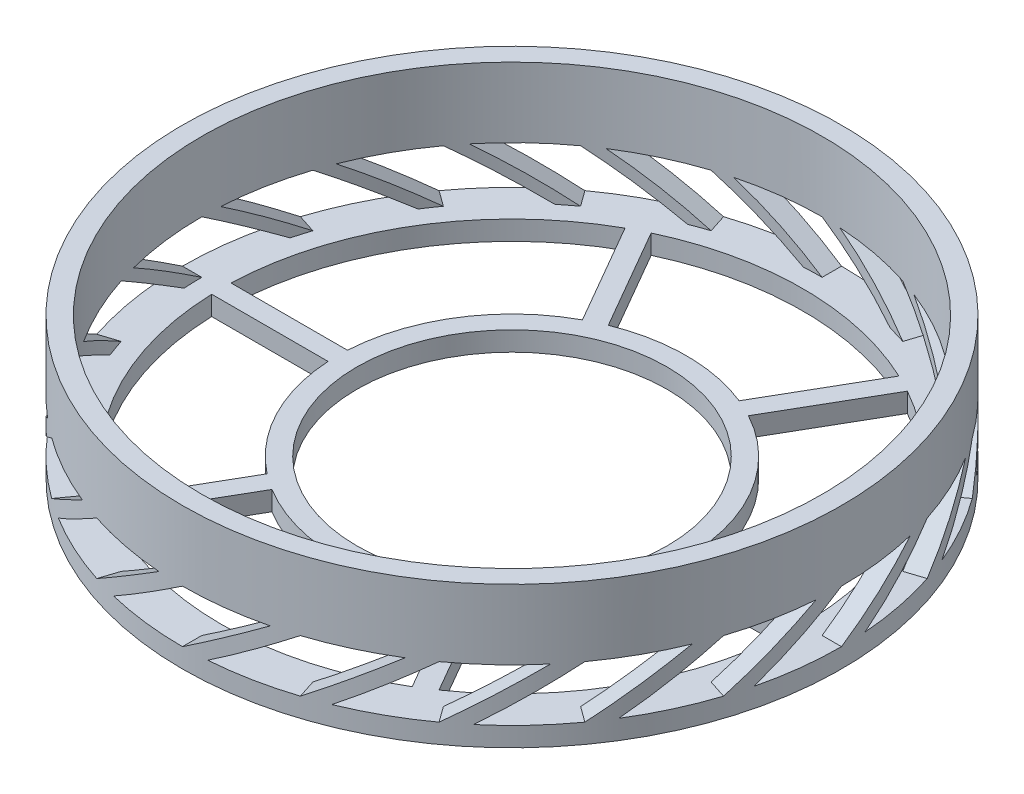
SolidWorks part; units mm, degrees
ref_plane "Front Plane" through (0, 0, 0) normal (0, 0, 1) x (1, 0, 0)
ref_plane "Top Plane" through (0, 0, 0) normal (0, 1, 0) x (1, 0, 0)
ref_plane "Right Plane" through (0, 0, 0) normal (1, 0, 0) x (0, 0, -1)
sketch "Sketch2" plane through (0, 0, 0) normal (0, 1, 0) x (1, 0, 0)
  circle A0 centre (0, 0) radius 26.9875
extrude "Boss-Extrude1" add sketch "Sketch2" along normal blind 11.5951
shell "Shell1" thickness 1.5875 removed face at (0, 11.5951, 26.9875)
ref_axis "Axis1" through (0, 11.5951, 0) along (0, -1, 0)
sketch "Sketch5" plane through (0, 1.5875, 0) normal (0, 1, 0) x (1, 0, 0)
  circle A0 centre (0, 0) radius 12.7
extrude "Cut-Extrude1" cut sketch "Sketch5" against normal through all both and the other way through all
sketch "Sketch6" plane through (0, 0, 0) normal (0, 0, 1) x (1, 0, 0)
  line L0 (0, 1.5875) -> (6.4136, 1.5875)
  line L1 (26.9875, 11.5951) -> (-26.9875, 11.5951) construction
  line L2 (0, 1.5875) -> (-6.4136, 5.8801)
  line L3 (0, 11.5951) -> (0, 8.356)
  line L8 (0, 0) -> (0, 1.5875)
  line L9 (0, 1.5875) -> (6.4136, 1.5875)
  line L13 (0, 1.5875) -> (0, 5.8801)
  line L14 (6.4136, 1.5875) -> (0, 5.8801)
  line L15 (-6.4136, 5.8801) -> (0, 5.8801)
extrude "Cut-Extrude2" cut sketch "Sketch6" against normal blind 38.1 contours L9 | L0 L2 L15 L14 region at (2.1379, 3.0184, 0)
pattern_circular "CirPattern3" count 20 over 360 about axis through (0, 11.5951, 0) along (0, -1, 0) of "Cut-Extrude2"
sketch "Sketch7" plane through (0, 1.5875, 0) normal (0, 1, 0) x (1, 0, 0)
  line L0 (-16.0509, -23.8323) -> (-14.6761, -24.626)
  line L1 (29.3522, -0.7937) -> (-29.3522, -0.7938)
  line L2 (29.3522, -0.7937) -> (29.3522, 0.7938)
  line L3 (29.3522, 0.7938) -> (-29.3522, 0.7937)
  line L4 (-29.3522, -0.7938) -> (-29.3522, 0.7937)
  line L5 (29.3522, -0.7937) -> (-29.3522, 0.7937) construction
  line L6 (29.3522, 0.7938) -> (-29.3522, -0.7938) construction
  line L7 (-16.0509, -23.8323) -> (13.3013, 27.0073)
  line L8 (13.3013, 27.0073) -> (14.6761, 26.2135)
  line L9 (-14.6761, -24.626) -> (14.6761, 26.2135)
  line L10 (-13.3013, 27.0073) -> (-14.6761, 26.2135)
  line L11 (-13.3013, 27.0073) -> (16.0509, -23.8323)
  line L12 (16.0509, -23.8323) -> (14.6761, -24.626)
  line L13 (-14.6761, 26.2135) -> (14.6761, -24.626)
  line L14 (0, 0.7938) -> (29.3522, -0.7937) construction
  circle A0 centre (0, 0) radius 14.2875
  circle A1 centre (0, 0) radius 23.8125
  dimension "D1" = 28.575
  dimension "D2" = 47.625
  dimension "D3" = 1.5875
  dimension "D5" = 29.3951
  dimension "D4" = 3
extrude "Cut-Extrude3" cut sketch "Sketch7" along normal through all both and the other way through all contours L1 A1 L7 A0 | L13 A1 L3 A0 | L7 A1 L11 A0 | L3 A1 L9 A0 | L11 A1 L1 A0 | L9 A1 L13 A0 region at (-16.6074, 1.5875, 8.9222) region at (0, 1.5875, 18.4872) region at (-15.8255, 1.5875, -9.7945) region at (16.6074, 1.5875, 8.9222) region at (0, 1.5875, -18.9707) region at (15.8255, 1.5875, -9.7945)
